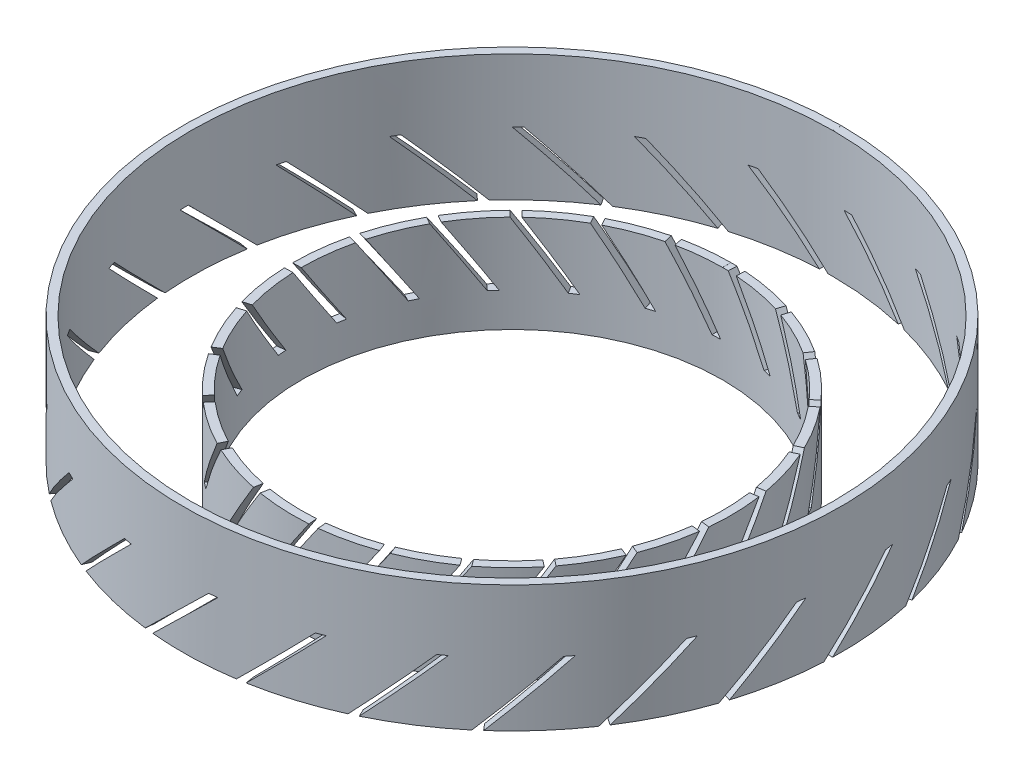
SolidWorks part; units mm, degrees
ref_plane "Front Plane" through (0, 0, 0) normal (0, 0, 1) x (1, 0, 0)
ref_plane "Top Plane" through (0, 0, 0) normal (0, 1, 0) x (1, 0, 0)
ref_plane "Right Plane" through (0, 0, 0) normal (1, 0, 0) x (0, 0, -1)
sketch "Sketch2" plane through (0, 0, 0) normal (0, 1, 0) x (1, 0, 0)
  line L0 (0, 0) -> (0, 33.8636)
  line L1 (0, 0) -> (0.0059, 33.8636)
  circle A0 centre (0, 0) radius 33
  circle A1 centre (0, 0) radius 33.8636
  dimension "D1" = 66
  dimension "D2" = 67.7272
  dimension "D3" = 0.01
extrude "Boss-Extrude1" add sketch "Sketch2" along normal blind 13 contours L0 A1 L1 A0 region at (-23.4023, 0, 23.4023)
surface "Surface-Flatten1"
sketch "Sketch3" plane through (0, 0, 0) normal (0, 1, 0) x (1, 0, 0)
  line L0 (0, 0) -> (0, 22.5)
  line L1 (0, 0) -> (0.0039, 22.5)
  circle A0 centre (0, 0) radius 22.5
  circle A1 centre (0, 0) radius 21.6364
  dimension "D1" = 0.8636
  dimension "D2" = 45
  dimension "D3" = 0.01
extrude "Boss-Extrude2" add sketch "Sketch3" along normal blind 6.5 and the other way blind 3.5 separate body contours A0 A1 region at (-15.7492, 0, 15.7492)
sketch "Sketch4" plane through (0, 0, 0) normal (0, 1, 0) x (1, 0, 0)
  line L0 (-0.8632, 44.9938) -> (0, 15.0062)
  line L1 (0, 15.0062) -> (-0.8632, 14.9814)
  line L2 (-0.8632, 14.9814) -> (-1.7265, 44.9689)
  line L3 (-1.7265, 44.9689) -> (-0.8632, 44.9938)
  line L4 (-0.4316, 14.9938) -> (0, 0) construction
  line L5 (10.47, 43.7672) -> (11.3079, 43.5582)
  line L6 (11.3079, 43.5582) -> (4.0486, 14.4497)
  line L7 (4.0486, 14.4497) -> (3.2107, 14.6587)
  line L8 (3.2107, 14.6587) -> (10.47, 43.7672)
  line L9 (21.89, 39.3194) -> (22.6405, 38.8921)
  line L10 (22.6405, 38.8921) -> (7.797, 12.8216)
  line L11 (7.797, 12.8216) -> (7.0465, 13.2489)
  line L12 (7.0465, 13.2489) -> (21.89, 39.3194)
  line L13 (31.6865, 31.9555) -> (32.2939, 31.3415)
  line L14 (32.2939, 31.3415) -> (10.9671, 10.2425)
  line L15 (10.9671, 10.2425) -> (10.3597, 10.8565)
  line L16 (10.3597, 10.8565) -> (31.6865, 31.9555)
  line L17 (39.133, 22.2216) -> (39.5522, 21.4665)
  line L18 (39.5522, 21.4665) -> (13.3238, 6.9038)
  line L19 (13.3238, 6.9038) -> (12.9046, 7.6589)
  line L20 (12.9046, 7.6589) -> (39.133, 22.2216)
  line L21 (43.6771, 10.8396) -> (43.8771, 9.9994)
  line L22 (43.8771, 9.9994) -> (14.6923, 3.0531)
  line L23 (14.6923, 3.0531) -> (14.4924, 3.8932)
  line L24 (14.4924, 3.8932) -> (43.6771, 10.8396)
  line L25 (44.9819, -1.3463) -> (44.9478, -2.2093)
  line L26 (44.9478, -2.2093) -> (14.9712, -1.0241)
  line L27 (14.9712, -1.0241) -> (15.0053, -0.1611)
  line L28 (15.0053, -0.1611) -> (44.9819, -1.3463)
  line L29 (42.9506, -13.4324) -> (42.685, -14.2541)
  line L30 (42.685, -14.2541) -> (14.1398, -5.0253)
  line L31 (14.1398, -5.0253) -> (14.4054, -4.2036)
  line L32 (14.4054, -4.2036) -> (42.9506, -13.4324)
  line L33 (37.7339, -24.5222) -> (37.2564, -25.2418)
  line L34 (37.2564, -25.2418) -> (12.2596, -8.6538)
  line L35 (12.2596, -8.6538) -> (12.7371, -7.9342)
  line L36 (12.7371, -7.9342) -> (37.7339, -24.5222)
  line L37 (29.7186, -33.7934) -> (29.0647, -34.3574)
  line L38 (29.0647, -34.3574) -> (9.4702, -11.6405)
  line L39 (9.4702, -11.6405) -> (10.1242, -11.0764)
  line L40 (10.1242, -11.0764) -> (29.7186, -33.7934)
  line L41 (19.4992, -40.5582) -> (18.7174, -40.9249)
  line L42 (18.7174, -40.9249) -> (5.9785, -13.7639)
  line L43 (5.9785, -13.7639) -> (6.7604, -13.3972)
  line L44 (6.7604, -13.3972) -> (19.4992, -40.5582)
  line L45 (7.8337, -44.315) -> (6.9819, -44.4572)
  line L46 (6.9819, -44.4572) -> (2.0433, -14.8664)
  line L47 (2.0433, -14.8664) -> (2.8952, -14.7243)
  line L48 (2.8952, -14.7243) -> (7.8337, -44.315)
  line L49 (-4.4129, -44.7852) -> (-5.2715, -44.6923)
  line L50 (-5.2715, -44.6923) -> (-2.0433, -14.8664)
  line L51 (-2.0433, -14.8664) -> (-1.1848, -14.9594)
  line L52 (-1.1848, -14.9594) -> (-4.4129, -44.7852)
  line L53 (-16.3321, -41.9339) -> (-17.1338, -41.6127)
  line L54 (-17.1338, -41.6127) -> (-5.9785, -13.7639)
  line L55 (-5.9785, -13.7639) -> (-5.1768, -14.085)
  line L56 (-5.1768, -14.085) -> (-16.3321, -41.9339)
  line L57 (-27.0401, -35.9725) -> (-27.7254, -35.447)
  line L58 (-27.7254, -35.447) -> (-9.4702, -11.6405)
  line L59 (-9.4702, -11.6405) -> (-8.7849, -12.166)
  line L60 (-8.7849, -12.166) -> (-27.0401, -35.9725)
  line L61 (-35.7426, -27.3432) -> (-36.2608, -26.6523)
  line L62 (-36.2608, -26.6523) -> (-12.2596, -8.6538)
  line L63 (-12.2596, -8.6538) -> (-11.7415, -9.3447)
  line L64 (-11.7415, -9.3447) -> (-35.7426, -27.3432)
  line L65 (-41.7943, -16.686) -> (-42.1068, -15.8809)
  line L66 (-42.1068, -15.8809) -> (-14.1398, -5.0253)
  line L67 (-14.1398, -5.0253) -> (-13.8273, -5.8304)
  line L68 (-13.8273, -5.8304) -> (-41.7943, -16.686)
  line L69 (-44.7463, -4.7912) -> (-44.83, -3.9317)
  line L70 (-44.83, -3.9317) -> (-14.9712, -1.0241)
  line L71 (-14.9712, -1.0241) -> (-14.8875, -1.8836)
  line L72 (-14.8875, -1.8836) -> (-44.7463, -4.7912)
  line L73 (-44.3796, 7.4588) -> (-44.2283, 8.3091)
  line L74 (-44.2283, 8.3091) -> (-14.6923, 3.0531)
  line L75 (-14.6923, 3.0531) -> (-14.8436, 2.2029)
  line L76 (-14.8436, 2.2029) -> (-44.3796, 7.4588)
  line L77 (-40.7216, 19.1557) -> (-40.3465, 19.9336)
  line L78 (-40.3465, 19.9336) -> (-13.3238, 6.9038)
  line L79 (-13.3238, 6.9038) -> (-13.6989, 6.1259)
  line L80 (-13.6989, 6.1259) -> (-40.7216, 19.1557)
  line L81 (-34.0433, 29.4319) -> (-33.4723, 30.0798)
  line L82 (-33.4723, 30.0798) -> (-10.9671, 10.2425)
  line L83 (-10.9671, 10.2425) -> (-11.5381, 9.5947)
  line L84 (-11.5381, 9.5947) -> (-34.0433, 29.4319)
  line L85 (-24.8403, 37.5253) -> (-24.1156, 37.995)
  line L86 (-24.1156, 37.995) -> (-7.797, 12.8216)
  line L87 (-7.797, 12.8216) -> (-8.5216, 12.3518)
  line L88 (-8.5216, 12.3518) -> (-24.8403, 37.5253)
  line L89 (-13.7949, 42.8356) -> (-12.9704, 43.0924)
  line L90 (-12.9704, 43.0924) -> (-4.0486, 14.4497)
  line L91 (-4.0486, 14.4497) -> (-4.8732, 14.1929)
  line L92 (-4.8732, 14.1929) -> (-13.7949, 42.8356)
  line L93 (0, 0) -> (0, 15.0062) construction
  point P98 (0, 0)
  dimension "D1" = 0.8636
  dimension "D2" = 15
  dimension "D3" = 30
  dimension "D4" = 23
sketch "Sketch5" plane through (0, 6.5, 0) normal (0, 1, 0) x (1, 0, 0)
  line L0 (-3.782, 14.5218) -> (-2.9404, 14.7153)
  line L1 (-3.782, 14.5218) -> (-10.5045, 43.7589)
  line L2 (-2.9404, 14.7153) -> (-9.6629, 43.9524)
  line L3 (-10.5045, 43.7589) -> (-9.6629, 43.9524)
  line L4 (-3.3612, 14.6186) -> (0, 0) construction
  line L5 (0, 0) -> (0, 11.9515) construction
  line L6 (0.2761, 15.0037) -> (1.1388, 14.9629)
  line L7 (0.2761, 15.0037) -> (1.691, 44.9703)
  line L8 (1.691, 44.9703) -> (2.5537, 44.9296)
  line L9 (1.1388, 14.9629) -> (2.5537, 44.9296)
  line L10 (4.3138, 14.3728) -> (5.1335, 14.1008)
  line L11 (4.3138, 14.3728) -> (13.7612, 42.8464)
  line L12 (13.7612, 42.8464) -> (14.5808, 42.5745)
  line L13 (5.1335, 14.1008) -> (14.5808, 42.5745)
  line L14 (8.0316, 12.676) -> (8.7475, 12.1929)
  line L15 (8.0316, 12.676) -> (24.8107, 37.5448)
  line L16 (24.8107, 37.5448) -> (25.5266, 37.0618)
  line L17 (8.7475, 12.1929) -> (25.5266, 37.0618)
  line L18 (11.1537, 10.039) -> (11.7127, 9.3807)
  line L19 (11.1537, 10.039) -> (34.0201, 29.4587)
  line L20 (34.0201, 29.4587) -> (34.5792, 28.8005)
  line L21 (11.7127, 9.3807) -> (34.5792, 28.8005)
  line L22 (13.4486, 6.6575) -> (13.8093, 5.8728)
  line L23 (13.4486, 6.6575) -> (40.7064, 19.1878)
  line L24 (40.7064, 19.1878) -> (41.0671, 18.4031)
  line L25 (13.8093, 5.8728) -> (41.0671, 18.4031)
  line L26 (14.746, 2.7822) -> (14.8817, 1.9293)
  line L27 (14.746, 2.7822) -> (44.3737, 7.4938)
  line L28 (44.3737, 7.4938) -> (44.5094, 6.6409)
  line L29 (14.8817, 1.9293) -> (44.5094, 6.6409)
  line L30 (14.9499, -1.2994) -> (14.8503, -2.1572)
  line L31 (14.9499, -1.2994) -> (44.7501, -4.756)
  line L32 (44.7501, -4.756) -> (44.6505, -5.6138)
  line L33 (14.8503, -2.1572) -> (44.6505, -5.6138)
  line L34 (14.0449, -5.2846) -> (13.7176, -6.0838)
  line L35 (14.0449, -5.2846) -> (41.8075, -16.653)
  line L36 (41.8075, -16.653) -> (41.4802, -17.4522)
  line L37 (13.7176, -6.0838) -> (41.4802, -17.4522)
  line L38 (12.0983, -8.8779) -> (11.5676, -9.5592)
  line L39 (12.0983, -8.8779) -> (35.7642, -27.315)
  line L40 (35.7642, -27.315) -> (35.2334, -27.9963)
  line L41 (11.5676, -9.5592) -> (35.2334, -27.9963)
  line L42 (9.2544, -11.8128) -> (8.5596, -12.3256)
  line L43 (9.2544, -11.8128) -> (27.0684, -35.9512)
  line L44 (27.0684, -35.9512) -> (26.3736, -36.464)
  line L45 (8.5596, -12.3256) -> (26.3736, -36.464)
  line L46 (5.7242, -13.8716) -> (4.9168, -14.1779)
  line L47 (5.7242, -13.8716) -> (16.3652, -41.921)
  line L48 (16.3652, -41.921) -> (15.5577, -42.2273)
  line L49 (4.9168, -14.1779) -> (15.5577, -42.2273)
  line L50 (1.7694, -14.9015) -> (0.9093, -14.9786)
  line L51 (1.7694, -14.9015) -> (4.4482, -44.7817)
  line L52 (4.4482, -44.7817) -> (3.588, -44.8588)
  line L53 (0.9093, -14.9786) -> (3.588, -44.8588)
  line L54 (-2.3166, -14.8263) -> (-3.1656, -14.6685)
  line L55 (-2.3166, -14.8263) -> (-7.7987, -44.3212)
  line L56 (-7.7987, -44.3212) -> (-8.6478, -44.1634)
  line L57 (-3.1656, -14.6685) -> (-8.6478, -44.1634)
  line L58 (-6.2308, -13.6515) -> (-7.0057, -13.2705)
  line L59 (-6.2308, -13.6515) -> (-19.4673, -40.5735)
  line L60 (-19.4673, -40.5735) -> (-20.2422, -40.1925)
  line L61 (-7.0057, -13.2705) -> (-20.2422, -40.1925)
  line L62 (-9.6828, -11.4643) -> (-10.3263, -10.8883)
  line L63 (-9.6828, -11.4643) -> (-29.692, -33.8168)
  line L64 (-29.692, -33.8168) -> (-30.3354, -33.2408)
  line L65 (-10.3263, -10.8883) -> (-30.3354, -33.2408)
  line L66 (-12.4168, -8.4267) -> (-12.881, -7.6985)
  line L67 (-12.4168, -8.4267) -> (-37.7146, -24.552)
  line L68 (-37.7146, -24.552) -> (-38.1788, -23.8237)
  line L69 (-12.881, -7.6985) -> (-38.1788, -23.8237)
  line L70 (-14.2298, -4.7642) -> (-14.4803, -3.9378)
  line L71 (-14.2298, -4.7642) -> (-42.94, -13.4662)
  line L72 (-42.94, -13.4662) -> (-43.1905, -12.6398)
  line L73 (-14.4803, -3.9378) -> (-43.1905, -12.6398)
  line L74 (-14.9875, -0.7484) -> (-15.0058, 0.115)
  line L75 (-14.9875, -0.7484) -> (-44.9809, -1.3818)
  line L76 (-44.9809, -1.3818) -> (-44.9991, -0.5184)
  line L77 (-15.0058, 0.115) -> (-44.9991, -0.5184)
  line L78 (-14.6337, 3.3229) -> (-14.4183, 4.1593)
  line L79 (-14.6337, 3.3229) -> (-43.6856, 10.8051)
  line L80 (-43.6856, 10.8051) -> (-43.4703, 11.6415)
  line L81 (-14.4183, 4.1593) -> (-43.4703, 11.6415)
  line L82 (-13.1945, 7.1478) -> (-12.7615, 7.895)
  line L83 (-13.1945, 7.1478) -> (-39.1505, 22.1907)
  line L84 (-39.1505, 22.1907) -> (-38.7174, 22.9379)
  line L85 (-12.7615, 7.895) -> (-38.7174, 22.9379)
  line L86 (-10.7767, 10.4426) -> (-10.1582, 11.0453)
  line L87 (-10.7767, 10.4426) -> (-31.7117, 31.9305)
  line L88 (-31.7117, 31.9305) -> (-31.0931, 32.5331)
  line L89 (-10.1582, 11.0453) -> (-31.0931, 32.5331)
  line L90 (-7.5597, 12.9629) -> (-6.8015, 13.3763)
  line L91 (-7.5597, 12.9629) -> (-21.921, 39.3021)
  line L92 (-21.921, 39.3021) -> (-21.1628, 39.7155)
  line L93 (-6.8015, 13.3763) -> (-21.1628, 39.7155)
  line L94 (-2.9404, 14.7153) -> (0, 0) construction
  point P99 (0, 0)
  dimension "D1" = 0.8636
  dimension "D2" = 30
  dimension "D3" = 11.3
  dimension "D4" = 15
  dimension "D5" = 23
loft "Cut-Loft1" cut section "Sketch4" section "Sketch5" connector at (-12.9704, 0, -43.0924) connector at (-21.1628, 6.5, -39.7155)
loft "Cut-Loft2" cut section "Sketch4<3>" section "Sketch5<3>" connector at (-24.1156, 0, -37.995) connector at (-31.0931, 6.5, -32.5331)
sketch "Sketch4<3>" plane through (0, 0, 0) normal (0, 1, 0) x (1, 0, 0) same geometry as "Sketch4"
sketch "Sketch5<3>" plane through (0, 6.5, 0) normal (0, 1, 0) x (1, 0, 0) same geometry as "Sketch5"
loft "Cut-Loft3" cut section "Sketch4<4>" section "Sketch5<4>" connector at (-33.4723, 0, -30.0798) connector at (-38.7174, 6.5, -22.9379)
sketch "Sketch4<4>" plane through (0, 0, 0) normal (0, 1, 0) x (1, 0, 0) same geometry as "Sketch4"
sketch "Sketch5<4>" plane through (0, 6.5, 0) normal (0, 1, 0) x (1, 0, 0) same geometry as "Sketch5"
loft "Cut-Loft4" cut section "Sketch4<5>" section "Sketch5<5>" connector at (-40.3465, 0, -19.9336) connector at (-43.4703, 6.5, -11.6415)
sketch "Sketch4<5>" plane through (0, 0, 0) normal (0, 1, 0) x (1, 0, 0) same geometry as "Sketch4"
sketch "Sketch5<5>" plane through (0, 6.5, 0) normal (0, 1, 0) x (1, 0, 0) same geometry as "Sketch5"
loft "Cut-Loft5" cut section "Sketch4<6>" section "Sketch5<6>" connector at (-44.2283, 0, -8.3091) connector at (-44.9991, 6.5, 0.5184)
sketch "Sketch4<6>" plane through (0, 0, 0) normal (0, 1, 0) x (1, 0, 0) same geometry as "Sketch4"
sketch "Sketch5<6>" plane through (0, 6.5, 0) normal (0, 1, 0) x (1, 0, 0) same geometry as "Sketch5"
loft "Cut-Loft6" cut section "Sketch4<7>" section "Sketch5<7>" connector at (-44.83, 0, 3.9317) connector at (-43.1905, 6.5, 12.6398)
sketch "Sketch4<7>" plane through (0, 0, 0) normal (0, 1, 0) x (1, 0, 0) same geometry as "Sketch4"
sketch "Sketch5<7>" plane through (0, 6.5, 0) normal (0, 1, 0) x (1, 0, 0) same geometry as "Sketch5"
loft "Cut-Loft7" cut section "Sketch4<8>" section "Sketch5<8>" connector at (-42.1068, 0, 15.8809) connector at (-38.1788, 6.5, 23.8237)
sketch "Sketch4<8>" plane through (0, 0, 0) normal (0, 1, 0) x (1, 0, 0) same geometry as "Sketch4"
sketch "Sketch5<8>" plane through (0, 6.5, 0) normal (0, 1, 0) x (1, 0, 0) same geometry as "Sketch5"
loft "Cut-Loft8" cut section "Sketch4<9>" section "Sketch5<9>" connector at (-36.2608, 0, 26.6523) connector at (-30.3354, 6.5, 33.2408)
sketch "Sketch4<9>" plane through (0, 0, 0) normal (0, 1, 0) x (1, 0, 0) same geometry as "Sketch4"
sketch "Sketch5<9>" plane through (0, 6.5, 0) normal (0, 1, 0) x (1, 0, 0) same geometry as "Sketch5"
loft "Cut-Loft9" cut section "Sketch4<10>" section "Sketch5<10>" connector at (-27.7254, 0, 35.447) connector at (-20.2422, 6.5, 40.1925)
sketch "Sketch4<10>" plane through (0, 0, 0) normal (0, 1, 0) x (1, 0, 0) same geometry as "Sketch4"
sketch "Sketch5<10>" plane through (0, 6.5, 0) normal (0, 1, 0) x (1, 0, 0) same geometry as "Sketch5"
loft "Cut-Loft10" cut section "Sketch4<11>" section "Sketch5<11>" connector at (-17.1338, 0, 41.6127) connector at (-8.6478, 6.5, 44.1634)
sketch "Sketch4<11>" plane through (0, 0, 0) normal (0, 1, 0) x (1, 0, 0) same geometry as "Sketch4"
sketch "Sketch5<11>" plane through (0, 6.5, 0) normal (0, 1, 0) x (1, 0, 0) same geometry as "Sketch5"
loft "Cut-Loft11" cut section "Sketch4<12>" section "Sketch5<12>" connector at (-5.2715, 0, 44.6923) connector at (3.588, 6.5, 44.8588)
sketch "Sketch4<12>" plane through (0, 0, 0) normal (0, 1, 0) x (1, 0, 0) same geometry as "Sketch4"
sketch "Sketch5<12>" plane through (0, 6.5, 0) normal (0, 1, 0) x (1, 0, 0) same geometry as "Sketch5"
loft "Cut-Loft12" cut section "Sketch4<13>" section "Sketch5<13>" connector at (6.9819, 0, 44.4572) connector at (15.5577, 6.5, 42.2273)
sketch "Sketch4<13>" plane through (0, 0, 0) normal (0, 1, 0) x (1, 0, 0) same geometry as "Sketch4"
sketch "Sketch5<13>" plane through (0, 6.5, 0) normal (0, 1, 0) x (1, 0, 0) same geometry as "Sketch5"
loft "Cut-Loft13" cut section "Sketch4<14>" section "Sketch5<14>" connector at (18.7174, 0, 40.9249) connector at (26.3736, 6.5, 36.464)
sketch "Sketch4<14>" plane through (0, 0, 0) normal (0, 1, 0) x (1, 0, 0) same geometry as "Sketch4"
sketch "Sketch5<14>" plane through (0, 6.5, 0) normal (0, 1, 0) x (1, 0, 0) same geometry as "Sketch5"
loft "Cut-Loft14" cut section "Sketch4<15>" section "Sketch5<15>" connector at (29.0647, 0, 34.3574) connector at (35.2334, 6.5, 27.9963)
sketch "Sketch4<15>" plane through (0, 0, 0) normal (0, 1, 0) x (1, 0, 0) same geometry as "Sketch4"
sketch "Sketch5<15>" plane through (0, 6.5, 0) normal (0, 1, 0) x (1, 0, 0) same geometry as "Sketch5"
loft "Cut-Loft15" cut section "Sketch4<16>" section "Sketch5<16>" connector at (37.2564, 0, 25.2418) connector at (41.4802, 6.5, 17.4522)
sketch "Sketch4<16>" plane through (0, 0, 0) normal (0, 1, 0) x (1, 0, 0) same geometry as "Sketch4"
sketch "Sketch5<16>" plane through (0, 6.5, 0) normal (0, 1, 0) x (1, 0, 0) same geometry as "Sketch5"
loft "Cut-Loft16" cut section "Sketch4<17>" section "Sketch5<17>" connector at (42.685, 0, 14.2541) connector at (44.6505, 6.5, 5.6138)
sketch "Sketch4<17>" plane through (0, 0, 0) normal (0, 1, 0) x (1, 0, 0) same geometry as "Sketch4"
sketch "Sketch5<17>" plane through (0, 6.5, 0) normal (0, 1, 0) x (1, 0, 0) same geometry as "Sketch5"
loft "Cut-Loft17" cut section "Sketch4<18>" section "Sketch5<18>" connector at (44.9478, 0, 2.2093) connector at (44.5094, 6.5, -6.6409)
sketch "Sketch4<18>" plane through (0, 0, 0) normal (0, 1, 0) x (1, 0, 0) same geometry as "Sketch4"
sketch "Sketch5<18>" plane through (0, 6.5, 0) normal (0, 1, 0) x (1, 0, 0) same geometry as "Sketch5"
loft "Cut-Loft18" cut section "Sketch4<19>" section "Sketch5<19>" connector at (43.8771, 0, -9.9994) connector at (41.0671, 6.5, -18.4031)
sketch "Sketch4<19>" plane through (0, 0, 0) normal (0, 1, 0) x (1, 0, 0) same geometry as "Sketch4"
sketch "Sketch5<19>" plane through (0, 6.5, 0) normal (0, 1, 0) x (1, 0, 0) same geometry as "Sketch5"
loft "Cut-Loft19" cut section "Sketch4<20>" section "Sketch5<20>" connector at (39.5522, 0, -21.4665) connector at (34.5792, 6.5, -28.8005)
sketch "Sketch4<20>" plane through (0, 0, 0) normal (0, 1, 0) x (1, 0, 0) same geometry as "Sketch4"
sketch "Sketch5<20>" plane through (0, 6.5, 0) normal (0, 1, 0) x (1, 0, 0) same geometry as "Sketch5"
loft "Cut-Loft20" cut section "Sketch4<21>" section "Sketch5<21>" connector at (32.2939, 0, -31.3415) connector at (25.5266, 6.5, -37.0618)
sketch "Sketch4<21>" plane through (0, 0, 0) normal (0, 1, 0) x (1, 0, 0) same geometry as "Sketch4"
sketch "Sketch5<21>" plane through (0, 6.5, 0) normal (0, 1, 0) x (1, 0, 0) same geometry as "Sketch5"
loft "Cut-Loft21" cut section "Sketch4<22>" section "Sketch5<22>" connector at (22.6405, 0, -38.8921) connector at (14.5808, 6.5, -42.5745)
sketch "Sketch4<22>" plane through (0, 0, 0) normal (0, 1, 0) x (1, 0, 0) same geometry as "Sketch4"
sketch "Sketch5<22>" plane through (0, 6.5, 0) normal (0, 1, 0) x (1, 0, 0) same geometry as "Sketch5"
loft "Cut-Loft22" cut section "Sketch4<23>" section "Sketch5<23>" connector at (11.3079, 0, -43.5582) connector at (2.5537, 6.5, -44.9296)
sketch "Sketch4<23>" plane through (0, 0, 0) normal (0, 1, 0) x (1, 0, 0) same geometry as "Sketch4"
sketch "Sketch5<23>" plane through (0, 6.5, 0) normal (0, 1, 0) x (1, 0, 0) same geometry as "Sketch5"
loft "Cut-Loft23" cut section "Sketch4<24>" section "Sketch5<24>" connector at (-0.8632, 0, -44.9938) connector at (-9.6629, 6.5, -43.9524)
sketch "Sketch4<24>" plane through (0, 0, 0) normal (0, 1, 0) x (1, 0, 0) same geometry as "Sketch4"
sketch "Sketch5<24>" plane through (0, 6.5, 0) normal (0, 1, 0) x (1, 0, 0) same geometry as "Sketch5"
